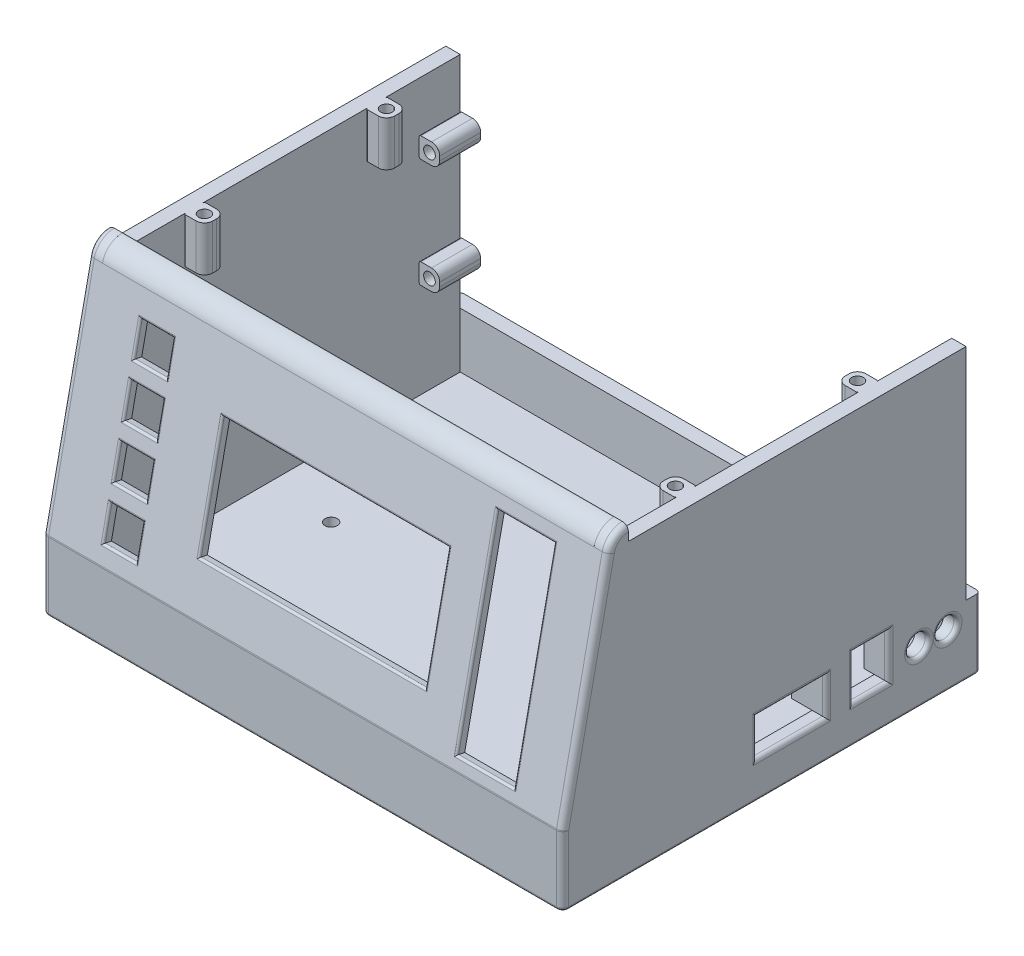
SolidWorks part; units mm, degrees
ref_plane "Front Plane" through (0, 0, 0) normal (0, 0, 1) x (1, 0, 0)
ref_plane "Top Plane" through (0, 0, 0) normal (0, 1, 0) x (1, 0, 0)
ref_plane "Right Plane" through (0, 0, 0) normal (1, 0, 0) x (0, 0, -1)
sketch "Sketch1" plane through (0, 0, 0) normal (0, 1, 0) x (1, 0, 0)
  line L1 (0, 0) -> (127, 0)
  line L2 (0, 0) -> (0, 102)
  line L3 (0, 102) -> (127, 102)
  line L4 (127, 0) -> (127, 102)
  line L5 (3.5, 98.5) -> (123.5, 98.5)
  line L6 (3.5, 98.5) -> (3.5, 3.5)
  line L7 (3.5, 3.5) -> (123.5, 3.5)
  line L8 (123.5, 98.5) -> (123.5, 3.5)
  dimension "D1" = 127
  dimension "D2" = 102
  dimension "D3" = 95
  dimension "D4" = 120
  dimension "D5" = 3.5
  dimension "D6" = 3.5
extrude "Boss-Extrude1" add sketch "Sketch1" along normal blind 13.5
sketch "Sketch3" plane through (0, 0, 0) normal (0, 1, 0) x (1, 0, 0)
  line L1 (0, 102) -> (127, 102)
  line L2 (0, 102) -> (0, 0)
  line L3 (0, 0) -> (127, 0)
  line L4 (127, 102) -> (127, 0)
extrude "Boss-Extrude2" add sketch "Sketch3" against normal blind 3.5
sketch "Sketch8" plane through (127, 0, 0) normal (1, 0, 0) x (0, 0, -1)
  line L1 (0, 13.5) -> (102, 13.5) construction
  line L6 (11.1658, 66.6754) -> (0, 13.5)
  line L8 (102, 13.5) -> (0, 13.5)
  line L9 (16.0591, 70.6479) -> (33.3532, 70.6479)
  line L10 (33.3532, 70.6479) -> (51, 70.6479)
  line L11 (51, 70.6479) -> (97, 70.6479)
  line L12 (102, 65.6479) -> (102, 13.5)
  arc A1 (11.1658, 66.6754) -> (16.0591, 70.6479) centre (16.0591, 65.6479) cw
  arc A2 (102, 65.6479) -> (97, 70.6479) centre (97, 65.6479) ccw
  dimension "D1" = 5
  dimension "D3" = 53.1754
  dimension "D4" = 102
extrude "Boss-Extrude3" add sketch "Sketch8" against normal blind 3.5
ref_plane "Plane2" through (63.5, 0, 0) normal (-1, 0, 0) x (0, 0, 1)
mirror "Mirror2" about plane through (63.5, 0, 0) normal (-1, 0, 0) of "Boss-Extrude3"
sketch "Sketch14" plane through (0, 0.5701, 2.715) normal (0, 0.2055, 0.9787) x (1, 0, 0)
  line L5 (3.5, 13.2119) -> (123.5, 13.2119)
  line L6 (3.5, 13.2119) -> (3.5, 67.5469)
  line L7 (3.5, 67.5469) -> (123.5, 67.5469)
  line L8 (123.5, 13.2119) -> (123.5, 67.5469)
extrude "Boss-Extrude4" add sketch "Sketch14" against normal blind 2
sketch "Sketch15" plane through (0, 0.5701, 2.715) normal (0, 0.2055, 0.9787) x (1, 0, 0)
  line L0 (0, 13.2119) -> (127, 13.2119) construction
  line L1 (35.9, 52.5469) -> (91.1, 52.5469)
  line L2 (35.9, 52.5469) -> (35.9, 24.9469)
  line L3 (35.9, 24.9469) -> (91.1, 24.9469)
  line L4 (91.1, 52.5469) -> (91.1, 24.9469)
  line L5 (14, 61.5469) -> (22, 61.5469)
  line L6 (14, 61.5469) -> (14, 53.5469)
  line L7 (14, 53.5469) -> (22, 53.5469)
  line L8 (22, 61.5469) -> (22, 53.5469)
  line L9 (14, 49.5469) -> (22, 49.5469)
  line L10 (14, 49.5469) -> (14, 41.5469)
  line L11 (14, 41.5469) -> (22, 41.5469)
  line L12 (22, 49.5469) -> (22, 41.5469)
  line L13 (14, 37.5469) -> (22, 37.5469)
  line L14 (14, 37.5469) -> (14, 29.5469)
  line L15 (14, 29.5469) -> (22, 29.5469)
  line L16 (22, 37.5469) -> (22, 29.5469)
  line L17 (14, 25.5469) -> (22, 25.5469)
  line L18 (14, 25.5469) -> (14, 17.5469)
  line L19 (14, 17.5469) -> (22, 17.5469)
  line L20 (22, 25.5469) -> (22, 17.5469)
  line L21 (100.5285, 64.2119) -> (114.5285, 64.2119)
  line L22 (100.5285, 64.2119) -> (100.5285, 16.2119)
  line L23 (100.5285, 16.2119) -> (114.5285, 16.2119)
  line L24 (114.5285, 64.2119) -> (114.5285, 16.2119)
  line L25 (123.5, 67.5469) -> (3.5, 67.5469) construction
  line L26 (127, 67.5469) -> (127, 13.2119) construction
  line L27 (127, 13.2119) -> (127, -3.4253) construction
  line L28 (0, 67.5469) -> (0, 13.2119) construction
  point P24 (107.5285, 16.2119)
  point P31 (14, 57.5469)
  point P34 (14, 33.5469)
  dimension "D1" = 48
  dimension "D2" = 14
  dimension "D3" = 3
  dimension "D4" = 55.2
  dimension "D5" = 27.6
  dimension "D6" = 8
  dimension "D7" = 8
  dimension "D8" = 8
  dimension "D9" = 8
  dimension "D10" = 8
  dimension "D11" = 8
  dimension "D12" = 8
  dimension "D13" = 8
  dimension "D14" = 15
  dimension "D15" = 35.9
  dimension "D16" = 4
  dimension "D17" = 4
  dimension "D18" = 4
  dimension "D19" = 14
  dimension "D20" = 14
  dimension "D21" = 14
  dimension "D22" = 14
  dimension "D23" = 6
extrude "Cut-Extrude1" cut sketch "Sketch15" against normal blind 3.5
sketch "Sketch17" plane through (0, 0, 0) normal (0, 1, 0) x (1, 0, 0)
  line L0 (123.5, 98.5) -> (3.5, 98.5) construction
  line L1 (123.5, 98.5) -> (3.5, 98.5) construction
  line L2 (123.5, 3.5) -> (123.5, 98.5) construction
  line L3 (123.5, 97) -> (123.5, 16.0591) construction
  line L4 (63.5, 36.9313) -> (63.5, -36.9313) construction
  circle A0 centre (103.5, 88.5) radius 1.5
  circle A1 centre (63.5, 88.5) radius 1.5
  circle A2 centre (19.5, 83.5) radius 1.5
  circle A3 centre (19.5, 51) radius 1.5
  circle A4 centre (19.5, 18.5) radius 1.5
  circle A5 centre (63.5, 13.5) radius 1.5
  circle A6 centre (103.5, 13.5) radius 1.5
  circle A7 centre (121, 83.5) radius 0.75
  circle A8 centre (32.5, 83.5) radius 0.75
  circle A9 centre (26, 18.5) radius 0.75
  circle A10 centre (121, 18.5) radius 0.75
  dimension "D1" = 3
  dimension "D2" = 3
  dimension "D3" = 3
  dimension "D4" = 3
  dimension "D5" = 3
  dimension "D6" = 3
  dimension "D7" = 3
  dimension "D22" = 1.5
  dimension "D23" = 1.5
  dimension "D24" = 1.5
  dimension "D25" = 1.5
  dimension "D8" = 10
  dimension "D9" = 10
  dimension "D10" = 15
  dimension "D11" = 20
  dimension "D12" = 20
  dimension "D13" = 75
  dimension "D14" = 40
  dimension "D15" = 32.5
  dimension "D16" = 2.5
  dimension "D17" = 75
  dimension "D18" = 40
  dimension "D19" = 44
  dimension "D20" = 44
  dimension "D21" = 44
  dimension "D26" = 2.5
  dimension "D27" = 15
  dimension "D28" = 15
  dimension "D29" = 88.5
  dimension "D30" = 97.5
  dimension "D31" = 65
  dimension "D33" = 65
extrude "Cut-Extrude3" cut sketch "Sketch17" against normal blind 3.5
sketch "Sketch19" plane through (127, 0, 0) normal (1, 0, 0) x (0, 0, -1)
  line L0 (16.0591, 70.6479) -> (16.0591, 67.1479)
  line L1 (16.0591, 67.1479) -> (98.5, 67.1479)
  line L2 (98.5, 67.1479) -> (98.5, 13.5)
  line L3 (98.5, 13.5) -> (102, 13.5)
  line L4 (102, 65.6479) -> (102, -3.5) construction
  line L5 (102, 13.5) -> (102, 65.6479)
  line L7 (97, 70.6479) -> (16.0591, 70.6479)
  arc A0 (97, 70.6479) -> (102, 65.6479) centre (97, 65.6479) cw
  dimension "D1" = 5
  dimension "D2" = 3.5
  dimension "D3" = 3.5
extrude "Cut-Extrude4" cut sketch "Sketch19" against normal blind 3.5
mirror "Mirror3" about plane through (63.5, 0, 0) normal (-1, 0, 0) of "Cut-Extrude4"
sketch "Sketch33" plane through (3.5, 0, 0) normal (1, 0, 0) x (0, 0, -1)
  line L0 (15.9807, 70.6279) -> (16.0591, 70.6479)
  line L1 (16.0591, 70.6479) -> (16.0591, 67.1479)
  arc A0 (15.9807, 70.6279) -> (11.1615, 66.6543) centre (16.0266, 65.663) ccw
  arc A1 (16.0591, 70.6479) -> (11.1658, 66.6754) centre (16.0591, 65.6479) ccw construction
  arc A3 (16.0591, 67.1479) -> (11.1615, 66.6543) centre (12.7983, 74.9584) cw
extrude "Boss-Extrude8" add sketch "Sketch33" along normal blind 120
sketch "Sketch35" plane through (127, 0, 0) normal (1, 0, 0) x (0, 0, -1)
  line L0 (0, -3.5) -> (102, -3.5) construction
  line L1 (71, 16.3) -> (79.6, 16.3)
  line L2 (71, 16.3) -> (71, 5.5)
  line L3 (71, 5.5) -> (79.6, 5.5)
  line L4 (79.6, 16.3) -> (79.6, 5.5)
  line L9 (102, 13.5) -> (102, -3.5) construction
  line L11 (47.43, 14.5) -> (64.43, 14.5)
  line L12 (47.43, 14.5) -> (47.43, 5.5)
  line L13 (47.43, 5.5) -> (64.43, 5.5)
  line L14 (64.43, 14.5) -> (64.43, 5.5)
  circle A0 centre (87, 9.5) radius 2.5
  circle A1 centre (94, 9.5) radius 2.5
  dimension "D9" = 5
  dimension "D10" = 5
  dimension "D1" = 8.6
  dimension "D2" = 10.8
  dimension "D3" = 13
  dimension "D4" = 22.4
  dimension "D5" = 17
  dimension "D6" = 9
  dimension "D7" = 37.57
  dimension "D8" = 9
  dimension "D11" = 13
  dimension "D12" = 8
  dimension "D13" = 7
  dimension "D14" = 9
extrude "Cut-Extrude5" cut sketch "Sketch35" against normal blind 5.5
sketch "Sketch37" plane through (123.5, 0, 0) normal (-1, 0, 0) x (0, 0, 1)
  line L12 (-79.6, 5.5) -> (-82.1, 5.5)
  line L13 (-82.1, 5.5) -> (-82.1, 18.8)
  line L14 (-82.1, 18.8) -> (-68.5, 18.8)
  line L15 (-68.5, 18.8) -> (-68.5, 5.5)
  line L16 (-68.5, 5.5) -> (-71, 5.5)
  line L17 (-71, 5.5) -> (-71, 16.3)
  line L18 (-71, 16.3) -> (-79.6, 16.3)
  line L19 (-79.6, 16.3) -> (-79.6, 5.5)
  dimension "D1" = 2.5
  dimension "D2" = 2.5
  dimension "D3" = 2.5
extrude "Boss-Extrude10" add sketch "Sketch37" along normal blind 2.5
sketch "Sketch38" plane through (123.5, 0, 0) normal (-1, 0, 0) x (0, 0, 1)
  line L0 (-64.43, 5.5) -> (-66.93, 5.5)
  line L1 (-66.93, 5.5) -> (-66.93, 17)
  line L2 (-66.93, 17) -> (-44.93, 17)
  line L3 (-44.93, 17) -> (-44.93, 5.5)
  line L4 (-44.93, 5.5) -> (-47.43, 5.5)
  line L5 (-47.43, 5.5) -> (-47.43, 14.5)
  line L6 (-47.43, 14.5) -> (-64.43, 14.5)
  line L7 (-64.43, 14.5) -> (-64.43, 5.5)
  dimension "D1" = 2.5
  dimension "D2" = 2.5
  dimension "D3" = 2.5
extrude "Boss-Extrude11" add sketch "Sketch38" along normal blind 5
sketch "Sketch40" plane through (0, 67.1479, 0) normal (0, 1, 0) x (1, 0, 0)
  line L0 (123.5, 3.5) -> (123.5, 98.5) construction
  line L1 (123.1, 31.0591) -> (120.5, 31.0591)
  line L2 (123.5, 31.4591) -> (123.5, 35.6591)
  line L3 (123.1, 36.0591) -> (120.5, 36.0591)
  line L4 (118.5, 33.0591) -> (118.5, 34.0591)
  line L5 (123.5, 68.5) -> (123.5, 82.1) construction
  line L6 (123.1, 75.5) -> (120.5, 75.5)
  line L7 (123.5, 75.9) -> (123.5, 80.1)
  line L8 (123.1, 80.5) -> (120.5, 80.5)
  line L9 (118.5, 77.5) -> (118.5, 78.5)
  line L11 (123.5, 16.0591) -> (127, 16.0591) construction
  line L12 (123.5, 98.5) -> (127, 98.5) construction
  line L13 (121, 68.5) -> (121, 82.1) construction
  arc A0 (118.5, 34.0591) -> (120.5, 36.0591) centre (120.5, 34.0591) cw
  arc A1 (118.5, 33.0591) -> (120.5, 31.0591) centre (120.5, 33.0591) ccw
  arc A2 (123.5, 31.4591) -> (123.1, 31.0591) centre (123.1, 31.4591) cw
  arc A3 (123.1, 36.0591) -> (123.5, 35.6591) centre (123.1, 35.6591) cw
  arc A4 (118.5, 78.5) -> (120.5, 80.5) centre (120.5, 78.5) cw
  arc A5 (118.5, 77.5) -> (120.5, 75.5) centre (120.5, 77.5) ccw
  arc A6 (123.5, 75.9) -> (123.1, 75.5) centre (123.1, 75.9) cw
  arc A7 (123.1, 80.5) -> (123.5, 80.1) centre (123.1, 80.1) cw
  circle A8 centre (121, 78) radius 1.425
  circle A10 centre (121, 33.5591) radius 1.425
  point P8 (118.5, 36.0591)
  point P11 (118.5, 31.0591)
  point P14 (123.5, 31.0591)
  point P17 (123.5, 36.0591)
  point P26 (118.5, 80.5)
  point P29 (118.5, 75.5)
  point P32 (123.5, 75.5)
  point P39 (125.25, 16.0591)
  dimension "D3" = 2
  dimension "D4" = 2
  dimension "D5" = 0.4
  dimension "D6" = 0.4
  dimension "D9" = 2
  dimension "D10" = 2
  dimension "D11" = 0.4
  dimension "D12" = 0.4
  dimension "D15" = 2.85
  dimension "D16" = 2.85
  dimension "D1" = 5
  dimension "D2" = 5
  dimension "D7" = 5
  dimension "D8" = 5
  dimension "D13" = 15
  dimension "D14" = 18
  dimension "D17" = 2.5
  dimension "D18" = 2.5
  dimension "D19" = 2.5
extrude "Boss-Extrude12" add sketch "Sketch40" against normal blind 11
mirror "Mirror4" about plane through (63.5, 0, 0) normal (-1, 0, 0) of "Boss-Extrude12"
sketch "Sketch41" plane through (0, 0, -98.5) normal (0, 0, -1) x (-1, 0, 0)
  line L0 (-123.5, 67.1479) -> (-123.5, 13.5) construction
  line L1 (-123.1, 55.1479) -> (-120.5, 55.1479)
  line L2 (-123.5, 54.7479) -> (-123.5, 50.5479)
  line L3 (-123.1, 50.1479) -> (-120.5, 50.1479)
  line L4 (-118.5, 53.1479) -> (-118.5, 52.1479)
  line L5 (-123.5, 67.1479) -> (-3.5, 67.1479) construction
  line L6 (-123.5, 13.5) -> (-123.5, 66.2644) construction
  line L7 (-123.1, 28.5) -> (-120.5, 28.5)
  line L8 (-123.5, 28.1) -> (-123.5, 23.9)
  line L9 (-123.1, 23.5) -> (-120.5, 23.5)
  line L10 (-118.5, 26.5) -> (-118.5, 25.5)
  line L11 (-3.5, 13.5) -> (-123.5, 13.5) construction
  arc A0 (-120.5, 55.1479) -> (-118.5, 53.1479) centre (-120.5, 53.1479) cw
  arc A1 (-120.5, 50.1479) -> (-118.5, 52.1479) centre (-120.5, 52.1479) ccw
  arc A2 (-123.5, 54.7479) -> (-123.1, 55.1479) centre (-123.1, 54.7479) cw
  arc A3 (-123.5, 50.5479) -> (-123.1, 50.1479) centre (-123.1, 50.5479) ccw
  arc A4 (-123.5, 28.1) -> (-123.1, 28.5) centre (-123.1, 28.1) cw
  arc A5 (-123.5, 23.9) -> (-123.1, 23.5) centre (-123.1, 23.9) ccw
  arc A6 (-118.5, 26.5) -> (-120.5, 28.5) centre (-120.5, 26.5) ccw
  arc A7 (-120.5, 23.5) -> (-118.5, 25.5) centre (-120.5, 25.5) ccw
  circle A8 centre (-121, 52.6479) radius 1.425
  circle A9 centre (-121, 26) radius 1.425
  point P8 (-118.5, 55.1479)
  point P11 (-118.5, 50.1479)
  point P14 (-123.5, 55.1479)
  point P27 (-123.5, 28.5)
  point P30 (-123.5, 23.5)
  point P33 (-118.5, 28.5)
  point P36 (-118.5, 23.5)
  dimension "D3" = 2
  dimension "D4" = 2
  dimension "D5" = 0.4
  dimension "D6" = 0.4
  dimension "D10" = 0.4
  dimension "D11" = 0.4
  dimension "D12" = 2
  dimension "D13" = 2
  dimension "D15" = 2.85
  dimension "D18" = 2.85
  dimension "D1" = 5
  dimension "D2" = 5
  dimension "D7" = 12
  dimension "D8" = 5
  dimension "D9" = 5
  dimension "D14" = 10
  dimension "D16" = 2.5
  dimension "D17" = 2.5
  dimension "D19" = 2.5
  dimension "D20" = 2.5
extrude "Boss-Extrude13" add sketch "Sketch41" against normal blind 10
mirror "Mirror5" about plane through (63.5, 0, 0) normal (-1, 0, 0) of "Boss-Extrude13"
fillet "Fillet12" radius 1.5 6 edges at (0, 69.5297, -12.9077) (127, 69.5297, -12.9077) (0, 40.0877, -5.5829) (127, 40.0877, -5.5829) (3.5, 39.8822, -7.5834) (123.5, 39.8822, -7.5834)
fillet "Fillet13" radius 1.5 5 edges at (0, 1.3504, 0) (0.4393, 11.3621, 0) (127, 1.3504, 0) (126.5607, 11.3621, 0) (63.5, 13.5, 0)
fillet "Fillet14" radius 1 1 edges at (127, 10, -47.43)
fillet "Fillet15" radius 1 3 edges at (127, 5.5, -55.43) (127, 10, -64.43) (127, 14.5, -55.43)
fillet "Fillet16" radius 1 4 edges at (127, 5.5, -75.3) (127, 10.9, -79.6) (127, 16.3, -75.3) (127, 10.9, -71)
fillet "Fillet17" radius 1 2 edges at (127, 9.5, -96.5) (127, 9.5, -89.5)
fillet "Fillet18" radius 1 1 edges at (127, 5, -102)
fillet "Fillet19" radius 1 1 edges at (0, 5, -102)
fillet "Fillet20" radius 0.5 1 edges at (14, 56.8888, -9.1108)
fillet "Fillet21" radius 0.5 23 edges at (114.5285, 39.9237, -5.5485) (107.5285, 63.4115, -10.4805) (100.5285, 39.9237, -5.5485) (107.5285, 16.436, -0.6165) (63.5, 24.9846, -2.4116) (91.1, 38.4901, -5.2475) (63.5, 51.9955, -8.0834) (35.9, 38.4901, -5.2475) (18, 25.5718, -2.5349) (22, 21.6572, -1.7129) (14, 21.6572, -1.7129) (18, 17.7425, -0.8909) (22, 33.4011, -4.1789) (18, 37.3157, -5.0009) (14, 33.4011, -4.1789) (18, 29.4864, -3.3569) (22, 45.1449, -6.6449) (18, 41.2303, -5.8229) (14, 45.1449, -6.6449) (18, 49.0596, -7.4669) (17.75, 52.9742, -8.2889) (22, 56.8888, -9.1108) (17.75, 60.8035, -9.9328)
fillet "Fillet23" radius 0.7 8 edges at (126.5607, -3.5, -0.4393) (63.5, -3.5, 0) (0.4393, -3.5, -0.4393) (0, -3.5, -51.25) (0.2929, -3.5, -101.7071) (63.5, -3.5, -102) (126.7071, -3.5, -101.7071) (127, -3.5, -51.25)
